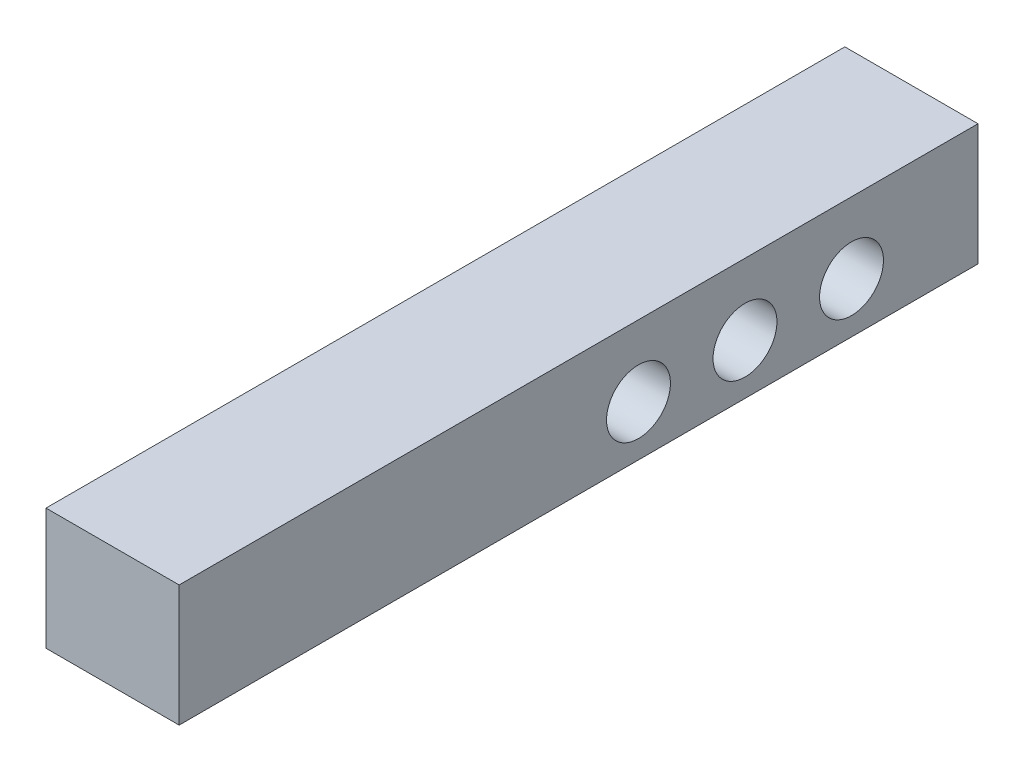
SolidWorks part; units mm, degrees
ref_plane "Alzado" through (0, 0, 0) normal (0, 0, 1) x (1, 0, 0)
ref_plane "Planta" through (0, 0, 0) normal (0, 1, 0) x (1, 0, 0)
ref_plane "Vista lateral" through (0, 0, 0) normal (1, 0, 0) x (0, 0, -1)
sketch "Croquis1" plane through (0, 0, 0) normal (0, 1, 0) x (1, 0, 0)
  line L1 (-10, 0) -> (0, 0)
  line L2 (-10, 0) -> (-10, -60)
  line L3 (-10, -60) -> (0, -60)
  line L4 (0, 0) -> (0, -60)
  dimension "D1" = 60
  dimension "D2" = 10
  dimension "D3" = 0
  dimension "D4" = 0
extrude "Saliente-Extruir1" add sketch "Croquis1" along normal blind 9.12
sketch "Croquis2" plane through (-10, 0, 0) normal (-1, 0, 0) x (0, 0, 1)
  line L0 (0, 0) -> (60, 0) construction
  line L1 (60, 9.12) -> (60, 0) construction
  circle A0 centre (17.5, 3.79) radius 2.4
  circle A1 centre (9.5, 3.79) radius 2.4
  circle A2 centre (25.5, 3.79) radius 2.4
  dimension "D1" = 3.79
  dimension "D2" = 42.5
  dimension "D3" = 4.8
  dimension "D4" = 4.8
  dimension "D5" = 8
  dimension "D6" = 8
  dimension "D7" = 4.8
  dimension "D8" = 3.79
  dimension "D9" = 3.79
extrude "Cortar-Extruir1" cut sketch "Croquis2" against normal through all
